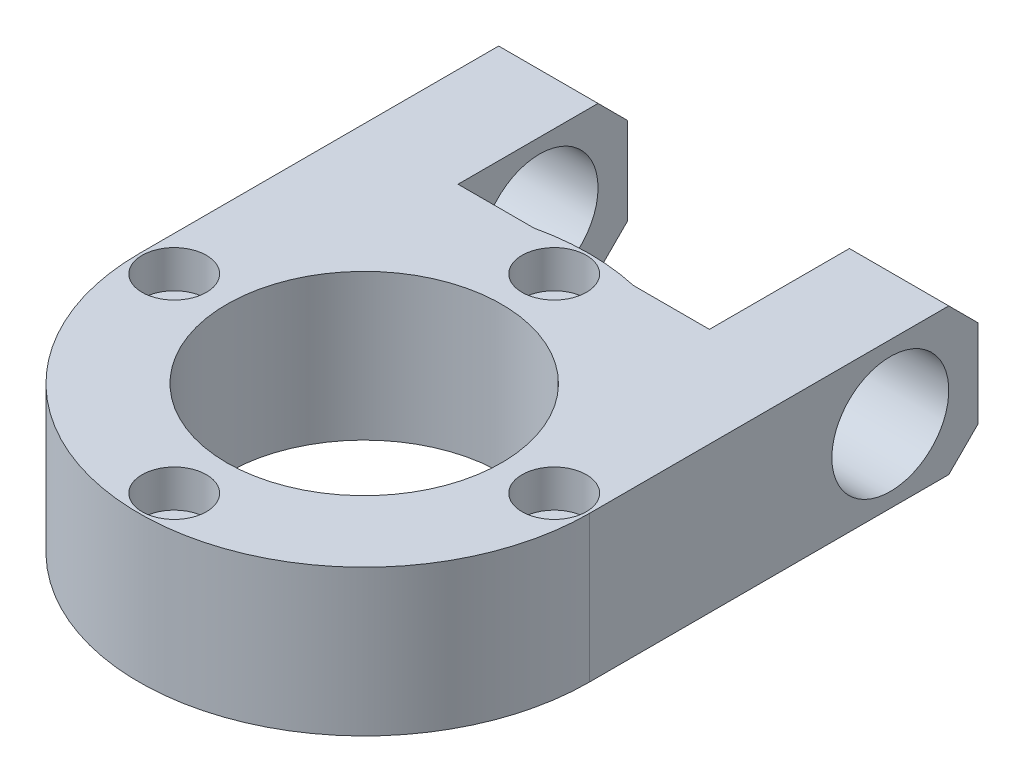
SolidWorks part; units mm, degrees
material "AISI 316 (1.4401)"
ref_plane "Płaszczyzna przednia" through (0, 0, 0) normal (0, 0, 1) x (1, 0, 0)
ref_plane "Płaszczyzna górna" through (0, 0, 0) normal (0, 1, 0) x (1, 0, 0)
ref_plane "Płaszczyzna prawa" through (0, 0, 0) normal (1, 0, 0) x (0, 0, -1)
sketch "Szkic1" plane through (0, 0, 0) normal (0, 1, 0) x (1, 0, 0)
  circle A0 centre (0, 0) radius 38.5
  circle A1 centre (0, 0) radius 23.5
  dimension "D1" = 77
  dimension "D2" = 47
extrude "Dodanie-wyciągnięcie1" add sketch "Szkic1" along normal blind 25
sketch "Szkic4" plane through (0, 25, 0) normal (0, 1, 0) x (1, 0, 0)
  line L0 (-8.5, 37.55) -> (-8.5, 66.5) construction
  line L1 (-8.5, 66.5) -> (8.5, 66.5) construction
  line L2 (8.5, 66.5) -> (8.5, 37.55) construction
  line L3 (-38.5, 0) -> (-38.5, 66.5)
  line L4 (-38.5, 66.5) -> (-21.5, 66.5)
  line L5 (-21.5, 66.5) -> (-21.5, 37.55)
  line L7 (38.5, 0) -> (38.5, 66.5)
  line L8 (38.5, 66.5) -> (21.5, 66.5)
  line L9 (21.5, 66.5) -> (21.5, 37.55)
  line L11 (-8.5, 37.55) -> (-21.5, 37.55)
  line L12 (8.5, 37.55) -> (21.5, 37.55)
  line L13 (-8.5, 37.55) -> (-38.5, 0)
  line L14 (8.5, 37.55) -> (38.5, 0)
  circle A0 centre (0, 0) radius 38.5 construction
  circle A1 centre (0, 0) radius 38.5 construction
  arc A2 (8.5, 37.55) -> (-8.5, 37.55) centre (0, 0) ccw construction
  dimension "D2" = 28
  dimension "D3" = 17
  dimension "D1" = 17
extrude "Dodanie-wyciągnięcie2" add sketch "Szkic4" against normal blind 25
hole_wizard "Pogłębienie walcowe pod M6 Wkręt z łbem walcowym z gniazdem sześciokątnym1" positions "Szkic2" profile "Szkic3" counterbore size "M6" standard "DIN" end condition up to next
sketch "Szkic2" plane through (0, 25, 0) normal (0, 1, 0) x (1, 0, 0)
  line L0 (0, 0) -> (0, 32.5) construction
  point P0 (0, 32.5)
  dimension "D1" = 32.5
sketch "Szkic3" plane through (0, 25, -32.5) normal (1, 0, 0) x (0, 0, 1)
  line L0 (0, 0) -> (0, 25)
  line L1 (0, 25) -> (3.3, 25)
  line L3 (3.3, 25) -> (3.3, 6.4)
  line L4 (3.3, 6.4) -> (5.5, 6.4)
  line L5 (5.5, 6.4) -> (5.5, 0)
  line L7 (5.5, 0) -> (0, 0)
  line L11 (0, -6.35) -> (0, 107.95) construction
  dimension "Średnica otworu na wylot" = 6.6
  dimension "Głębokość otworu na wylot" = 25
  dimension "Średnica pogłębienia walcowego" = 11
  dimension "Głębokość pogłębienia walcowego" = 6.4
hole_wizard "Otwór Ø20.0 (20)1" positions "Szkic5" profile "Szkic6" hole size "Ø20.0" standard "DIN" end condition through all
sketch "Szkic5" plane through (-38.5, 0, 0) normal (-1, 0, 0) x (0, 0, 1)
  line L0 (-66.5, 12.5) -> (-51.5, 12.5) construction
  line L2 (-66.5, 0) -> (-66.5, 25) construction
  point P0 (-51.5, 12.5)
  point P7 (-63.5, 12.5)
  dimension "D1" = 15
sketch "Szkic6" plane through (-38.5, 12.5, -51.5) normal (0, 1, 0) x (0, 0, 1)
  line L0 (0, 0) -> (0, 77)
  line L1 (0, 77) -> (10, 77)
  line L2 (10, 77) -> (10, 0)
  line L5 (10, 0) -> (0, 0)
  line L11 (0, -6.35) -> (0, 107.95) construction
  dimension "Średnica otworu na wylot" = 20
  dimension "Głębokość otworu na wylot" = 77
pattern_circular "Szyk kołowy1" count 4 over 360 about axis through (0, 25, 0) along (0, -1, 0) of "Pogłębienie walcowe pod M6 Wkręt z łbem walcowym z gniazdem sześciokątnym1"
chamfer "Sfazowanie1" distance 5 angle 45 4 edges at (-30, 0, -66.5) (-30, 25, -66.5) (30, 0, -66.5) (30, 25, -66.5)
